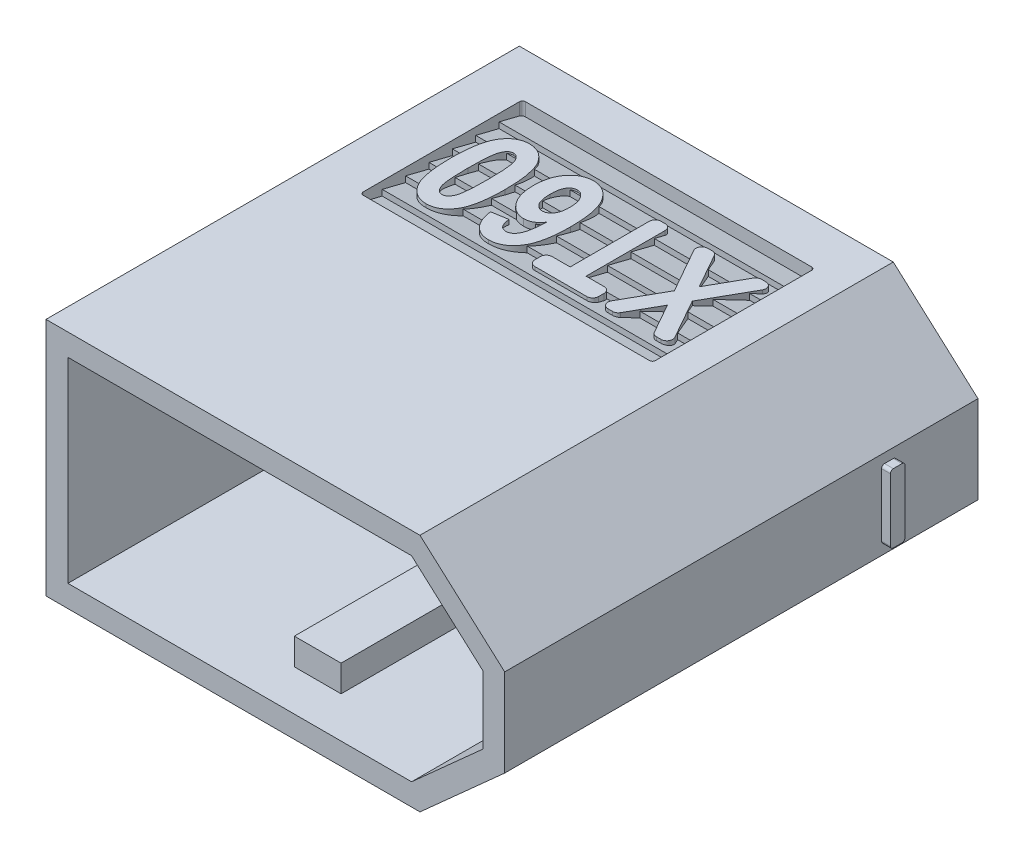
SolidWorks part; units mm, degrees
material "Nylon 101"
ref_plane "Plano frontal" through (0, 0, 0) normal (0, 0, 1) x (1, 0, 0)
ref_plane "Plano superior" through (0, 0, 0) normal (0, 1, 0) x (1, 0, 0)
ref_plane "Plano direito" through (0, 0, 0) normal (1, 0, 0) x (0, 0, -1)
sketch "Esboço1" plane through (0, 0, 0) normal (0, 0, 1) x (1, 0, 0)
  line L0 (0, 0) -> (12.8, 0)
  line L1 (12.8, 0) -> (15.7, 2.6)
  line L2 (15.7, 2.6) -> (15.7, 5.6)
  line L3 (15.7, 5.6) -> (12.8, 8.2)
  line L4 (12.8, 8.2) -> (0, 8.2)
  line L5 (0, 8.2) -> (0, 0)
  dimension "D1" = 12.8
  dimension "D2" = 3
  dimension "D3" = 15.7
  dimension "D4" = 8.2
extrude "Ressalto-extrusão1" add sketch "Esboço1" along normal blind 16.2
sketch "Esboço2" plane through (0, 0, 16.2) normal (0, 0, 1) x (1, 0, 0)
  line L0 (0.75, 7.45) -> (0.75, 0.75)
  line L1 (0.75, 0.75) -> (12.513, 0.75)
  line L2 (12.513, 0.75) -> (14.95, 2.9349)
  line L3 (14.95, 2.9349) -> (14.95, 5.2651)
  line L4 (14.95, 5.2651) -> (12.513, 7.45)
  line L5 (12.513, 7.45) -> (0.75, 7.45)
  line L6 (0, 8.2) -> (0, 0)
  line L7 (0, 0) -> (12.8, 0)
  line L8 (12.8, 0) -> (15.7, 2.6)
  line L9 (15.7, 2.6) -> (15.7, 5.6)
  line L10 (15.7, 5.6) -> (12.8, 8.2)
  line L11 (12.8, 8.2) -> (0, 8.2)
  line L12 (0, 8.2) -> (0, 0) construction
  line L13 (0, 0) -> (12.8, 0) construction
  line L14 (12.8, 0) -> (15.7, 2.6) construction
  line L15 (15.7, 2.6) -> (15.7, 5.6) construction
  line L16 (15.7, 5.6) -> (12.8, 8.2) construction
  line L17 (12.8, 8.2) -> (0, 8.2) construction
  dimension "D1" = 0
  dimension "D2" = 0.75
extrude "Corte-extrusão1" cut sketch "Esboço2" against normal blind 9.4
sketch "Esboço3" plane through (0, 0, 6.8) normal (0, 0, 1) x (1, 0, 0)
  line L1 (7.1, 1.66) -> (8.7, 1.66)
  line L2 (7.1, 1.66) -> (7.1, 0.75)
  line L3 (7.1, 0.75) -> (8.7, 0.75)
  line L4 (8.7, 1.66) -> (8.7, 0.75)
  line L7 (0.75, 0.75) -> (12.513, 0.75) construction
  line L8 (0, 0) -> (12.8, 0) construction
  line L9 (0, 8.2) -> (0, 0) construction
  dimension "D1" = 1.6
  dimension "D2" = 1.66
  dimension "D3" = 8.7
extrude "Ressalto-extrusão2" add sketch "Esboço3" along normal blind 8
sketch "Esboço4" plane through (0, 0, 6.8) normal (0, 0, 1) x (1, 0, 0)
  line L0 (12.513, 7.45) -> (0.75, 7.45) construction
  line L1 (8.7, 1.75) -> (7.1, 1.75)
  line L2 (8.7, 1.75) -> (8.7, 6.45)
  line L3 (8.7, 6.45) -> (7.1, 6.45)
  line L4 (7.1, 1.75) -> (7.1, 6.45)
  line L5 (0.75, 0.75) -> (7.1, 0.75) construction
  line L7 (7.1, 1.66) -> (7.1, 0.75) construction
  line L8 (8.7, 0.75) -> (8.7, 1.66) construction
  dimension "D1" = 1
  dimension "D2" = 1
extrude "Corte-extrusão2" cut sketch "Esboço4" against normal blind 1.5
sketch "Esboço5" plane through (0, 0, 0) normal (0, 0, -1) x (-1, 0, 0)
  line L0 (-15.7, 2.6) -> (-15.7, 5.6) construction
  line L3 (0, 8.2) -> (0, 0) construction
  circle A0 centre (-11.35, 4.1) radius 3
  circle A1 centre (-4.25, 4.1) radius 3
  point P6 (-15.7, 4.1)
  point P9 (-15.7, 4.1)
  dimension "D1" = 6
  dimension "D3" = 4.25
  dimension "D2" = 4.35
extrude "Corte-extrusão3" cut sketch "Esboço5" against normal blind 2
sketch "Esboço6" plane through (0, 0, 2) normal (0, 0, -1) x (-1, 0, 0)
  line L0 (-15.7, 2.6) -> (-15.7, 5.6) construction
  line L3 (0, 8.2) -> (0, 0) construction
  circle A0 centre (-11.35, 4.1) radius 2.15
  circle A2 centre (-4.25, 4.1) radius 2.15
  point P4 (-15.7, 4.1)
  dimension "D1" = 4.3
  dimension "D2" = 6.5
  dimension "D3" = 6.4
extrude "Corte-extrusão4" cut sketch "Esboço6" against normal through all
sketch "Esboço7" plane through (0, 0, 0) normal (-1, 0, 0) x (0, 0, 1)
  line L0 (2.8, 4.35) -> (2.05, 4.35)
  line L1 (4.25, 4.35) -> (3.5, 4.35)
  line L2 (4.35, 4.25) -> (4.35, 3.95)
  line L3 (4.25, 3.85) -> (3.5, 3.85)
  line L4 (1.95, 4.25) -> (1.95, 3.95)
  line L5 (3.3, 5.3) -> (3, 5.3)
  line L6 (3.4, 5.2) -> (3.4, 4.45)
  line L7 (3.3, 2.9) -> (3, 2.9)
  line L8 (2.9, 5.2) -> (2.9, 4.45)
  line L9 (2.8, 3.85) -> (2.05, 3.85)
  line L10 (3.4, 3.75) -> (3.4, 3)
  line L11 (2.9, 3.75) -> (2.9, 3)
  line L12 (0, 8.2) -> (0, 0) construction
  arc A0 (3, 2.9) -> (2.9, 3) centre (3, 3) cw
  arc A1 (3.3, 5.3) -> (3.4, 5.2) centre (3.3, 5.2) cw
  arc A2 (3, 5.3) -> (2.9, 5.2) centre (3, 5.2) ccw
  arc A3 (2.05, 4.35) -> (1.95, 4.25) centre (2.05, 4.25) ccw
  arc A4 (2.05, 3.85) -> (1.95, 3.95) centre (2.05, 3.95) cw
  arc A5 (2.8, 3.85) -> (2.9, 3.75) centre (2.8, 3.75) cw
  arc A6 (2.8, 4.35) -> (2.9, 4.45) centre (2.8, 4.45) ccw
  arc A7 (3.5, 3.85) -> (3.4, 3.75) centre (3.5, 3.75) ccw
  arc A8 (3.4, 3) -> (3.3, 2.9) centre (3.3, 3) cw
  arc A9 (4.35, 3.95) -> (4.25, 3.85) centre (4.25, 3.95) cw
  arc A10 (4.25, 4.35) -> (4.35, 4.25) centre (4.25, 4.25) cw
  arc A11 (3.5, 4.35) -> (3.4, 4.45) centre (3.5, 4.45) cw
  point P12 (1.95, 4.1)
  point P15 (0, 4.1)
  point P28 (2.9, 3.85)
  point P33 (3.4, 3.85)
  point P38 (4.35, 3.85)
  point P41 (4.35, 4.35)
  dimension "D4" = 0.1
  dimension "D1" = 2.4
  dimension "D2" = 0.5
  dimension "D3" = 4.35
extrude "Ressalto-extrusão3" add sketch "Esboço7" along normal blind 0.3
sketch "Esboço8" plane through (15.7, 0, 0) normal (1, 0, 0) x (0, 0, -1)
  line L0 (0, 2.6) -> (0, 5.6) construction
  line L1 (-3.2, 2.925) -> (-2.9, 2.925)
  line L2 (-3.3, 3.025) -> (-3.3, 5.175)
  line L3 (-3.2, 5.275) -> (-2.9, 5.275)
  line L4 (-2.8, 3.025) -> (-2.8, 5.175)
  arc A0 (-3.3, 5.175) -> (-3.2, 5.275) centre (-3.2, 5.175) cw
  arc A1 (-2.9, 5.275) -> (-2.8, 5.175) centre (-2.9, 5.175) cw
  arc A2 (-3.2, 2.925) -> (-3.3, 3.025) centre (-3.2, 3.025) cw
  arc A3 (-2.9, 2.925) -> (-2.8, 3.025) centre (-2.9, 3.025) ccw
  point P4 (-2.8, 4.1)
  point P7 (0, 4.1)
  point P10 (-3.3, 5.275)
  point P13 (-2.8, 5.275)
  point P18 (-2.8, 2.925)
  dimension "D4" = 0.1
  dimension "D1" = 2.35
  dimension "D2" = 0.5
  dimension "D3" = 3.3
extrude "Ressalto-extrusão4" add sketch "Esboço8" along normal blind 0.3
sketch "Esboço9" plane through (0, 0, 0) normal (0, -1, 0) x (1, 0, 0)
  line L0 (12.8, 16.2) -> (12.8, 0) construction
  line L1 (1.75, 7.0931) -> (11.55, 7.0931)
  line L2 (1.65, 6.9931) -> (1.65, 1.6431)
  line L3 (1.75, 1.5431) -> (11.55, 1.5431)
  line L4 (11.65, 6.9931) -> (11.65, 1.6431)
  arc A0 (1.65, 1.6431) -> (1.75, 1.5431) centre (1.75, 1.6431) ccw
  arc A1 (11.55, 1.5431) -> (11.65, 1.6431) centre (11.55, 1.6431) ccw
  arc A2 (11.55, 7.0931) -> (11.65, 6.9931) centre (11.55, 6.9931) cw
  arc A3 (1.75, 7.0931) -> (1.65, 6.9931) centre (1.75, 6.9931) ccw
  dimension "D1" = 0.1
  dimension "D2" = 1.15
  dimension "D3" = 10
  dimension "D4" = 5.55
extrude "Corte-extrusão5" cut sketch "Esboço9" against normal blind 0.75
sketch "Esboço10" plane through (1.65, 0, 0) normal (1, 0, 0) x (0, 0, -1)
  line L0 (-6.8, 0.75) -> (-1.6431, 0.75) construction
  line L1 (-1.5431, 0.75) -> (-1.5431, 0) construction
  line L2 (-3.1431, 0.25) -> (-2.3431, 0.45)
  line L3 (-2.3431, 0.45) -> (-2.3431, 0.25)
  line L5 (-3.1431, 0.45) -> (-3.1431, 0.25)
  line L6 (-2.3431, 0.45) -> (-2.3431, 0.25)
  line L7 (-3.9431, 0.25) -> (-3.1431, 0.45)
  line L8 (-3.9431, 0.45) -> (-3.9431, 0.25)
  line L9 (-4.7431, 0.25) -> (-3.9431, 0.45)
  line L10 (-4.7431, 0.45) -> (-4.7431, 0.25)
  line L11 (-5.5431, 0.25) -> (-4.7431, 0.45)
  line L12 (-5.5431, 0.45) -> (-5.5431, 0.25)
  line L13 (-6.3431, 0.25) -> (-5.5431, 0.45)
  line L14 (-6.3431, 0.45) -> (-6.3431, 0.25)
  line L15 (-7.1431, 0.25) -> (-6.3431, 0.45)
  line L16 (-7.1431, 0.45) -> (-7.1431, 0.25)
  line L17 (-7.1431, 0.45) -> (-7.1431, 0.75)
  line L19 (-2.3431, 0.25) -> (-1.5431, 0.45)
  line L20 (-7.1431, 0.75) -> (-1.5431, 0.75)
  line L21 (-1.5431, 0.45) -> (-1.5431, 0.75)
  line L31 (-2.3431, 0.25) -> (-1.5431, 0.45)
  line M62 (-1.6431, 0) -> (-1.6431, 0.75)
  line M63 (-1.6431, 0.75) -> (-6.8, 0.75)
  line M64 (-6.8, 0.75) -> (-6.9931, 0.75)
  line M65 (-6.9931, 0.75) -> (-6.9931, 0)
  dimension "D1" = 0.8
  dimension "D2" = 0.2
  dimension "D3" = 0.3
  dimension "D4" = 7
extrude "Ressalto-extrusão7" add sketch "Esboço10" along normal up to surface (10 mm away) contours L3 M65 M62 M63 M64 | M62 | M65 region at (1.65, 0.5464, 4.3262) region at (1.65, 0.5937, 1.5938) region at (1.65, 0.5093, 7.0691) up to face at (11.65, 0.45, 4.8145)
ref_plane "Plano1" through (0, 4.1, 0) normal (0, 1, 0) x (1, 0, 0)
mirror "Espelhar1" about plane through (0, 4.1, 0) normal (0, 1, 0) of "Corte-extrusão5", "Ressalto-extrusão7"
ref_plane "Plano2" through (0, 0.5, 0) normal (0, -1, 0) x (-1, 0, 0)
sketch "Esboço11" plane through (0, 0.5, 0) normal (0, -1, 0) x (-1, 0, 0)
  line L1 (-2.131, -7.0931) -> (-2.131, -1.5431) construction
  line L2 (-11.55, -7.0931) -> (-1.75, -7.0931) construction
  line L3 (-11.55, -1.5431) -> (-1.75, -1.5431) construction
  line L4 (-0.85, -6.1831) -> (-0.85, -2.4531) construction
  line L5 (-0.85, -2.4531) -> (-11.65, -2.4531) construction
  line L8 (-11.65, -3.1431) -> (-11.65, -2.3431) construction
  line L10 (-1.65, -6.9931) -> (-1.65, -1.6431) construction
  text T0 "<b><i>TGY</i></b>" font "Calibri" height in points 14
  point P8 (-0.85, -4.3181)
  point P9 (-2.131, -4.3181)
  dimension "D2" = 0.8
  dimension "D1" = 3.73
extrude "Ressalto-extrusão8" add sketch "Esboço11" along normal blind 0.3
ref_plane "Plano3" through (0, 7.7, 0) normal (0, 1, 0) x (1, 0, 0)
sketch "Esboço12" plane through (0, 7.7, 0) normal (0, 1, 0) x (1, 0, 0)
  line L0 (11.0942, -7.0931) -> (11.0942, -1.5431) construction
  line L1 (11.55, -7.0931) -> (1.75, -7.0931) construction
  line L3 (11.3535, -6.0681) -> (11.3535, -2.5681) construction
  line L6 (11.3535, -2.5681) -> (1.9746, -2.5681) construction
  line L7 (11.185, -2.8665) -> (10.3201, -4.3984)
  line L8 (10.3201, -4.3984) -> (11.0942, -5.7698)
  line L9 (10.92, -6.0681) -> (10.7649, -6.0681)
  line L10 (10.5908, -5.9665) -> (10.0126, -4.9431)
  line L11 (10.0126, -4.9431) -> (9.435, -5.9664)
  line L12 (9.2609, -6.0681) -> (9.1051, -6.0681)
  line L13 (8.931, -5.7698) -> (9.705, -4.3984)
  line L14 (9.705, -4.3984) -> (8.8401, -2.8665)
  line L15 (9.0143, -2.5681) -> (9.1699, -2.5681)
  line L16 (9.3441, -2.6698) -> (10.0126, -3.8543)
  line L17 (10.0126, -3.8543) -> (10.6817, -2.6698)
  line L18 (10.8559, -2.5681) -> (11.0109, -2.5681)
  line L19 (7.7626, -2.7681) -> (7.7626, -5.4772)
  line L20 (7.7626, -5.4772) -> (8.3808, -5.4772)
  line L21 (8.5808, -5.6772) -> (8.5808, -5.8681)
  line L22 (8.3808, -6.0681) -> (6.5989, -6.0681)
  line L23 (6.3989, -5.8681) -> (6.3989, -5.6772)
  line L24 (6.5989, -5.4772) -> (7.2171, -5.4772)
  line L25 (7.2171, -5.4772) -> (7.2171, -2.7681)
  line L26 (7.4171, -2.5681) -> (7.5626, -2.5681)
  line L27 (4.2171, -5.2045) -> (4.7626, -5.1136)
  line L28 (11.55, -1.5431) -> (1.75, -1.5431) construction
  arc A0 (7.2171, -2.7681) -> (7.4171, -2.5681) centre (7.4171, -2.7681) cw
  arc A1 (7.7626, -2.7681) -> (7.5626, -2.5681) centre (7.5626, -2.7681) ccw
  arc A2 (6.3989, -5.6772) -> (6.5989, -5.4772) centre (6.5989, -5.6772) cw
  arc A3 (6.5989, -6.0681) -> (6.3989, -5.8681) centre (6.5989, -5.8681) cw
  arc A4 (8.5808, -5.8681) -> (8.3808, -6.0681) centre (8.3808, -5.8681) cw
  arc A5 (8.3808, -5.4772) -> (8.5808, -5.6772) centre (8.3808, -5.6772) cw
  arc A6 (11.185, -2.8665) -> (11.0109, -2.5681) centre (11.0109, -2.7681) ccw
  arc A7 (10.6817, -2.6698) -> (10.8559, -2.5681) centre (10.8559, -2.7681) cw
  arc A8 (9.1699, -2.5681) -> (9.3441, -2.6698) centre (9.1699, -2.7681) cw
  arc A9 (8.8401, -2.8665) -> (9.0143, -2.5681) centre (9.0143, -2.7681) cw
  arc A10 (9.1051, -6.0681) -> (8.931, -5.7698) centre (9.1051, -5.8681) cw
  arc A11 (9.435, -5.9664) -> (9.2609, -6.0681) centre (9.2609, -5.8681) cw
  arc A12 (10.7649, -6.0681) -> (10.5908, -5.9665) centre (10.7649, -5.8681) cw
  arc A13 (11.0942, -5.7698) -> (10.92, -6.0681) centre (10.92, -5.8681) cw
  spline S0 degree 3 poles (4.7626, -5.1136) (4.7682, -5.1739) (4.7813, -5.2594) (4.8192, -5.3612) (4.8534, -5.4198) (4.8944, -5.4666) (4.9618, -5.511) (5.022, -5.5233) (5.0623, -5.5227) knots 0 0 0 0 0.323351 0.457032 0.575726 0.682828 0.785622 1 1 1 1
  spline S1 degree 3 poles (5.0623, -5.5227) (5.09, -5.5233) (5.1312, -5.5165) (5.1832, -5.4965) (5.2201, -5.4751) (5.2548, -5.4474) (5.2873, -5.4137) (5.3188, -5.3744) (5.3485, -5.328) (5.3759, -5.2719) (5.4005, -5.2044) (5.4208, -5.1242) (5.4414, -5.0325) (5.4567, -4.9277) (5.4769, -4.7639) (5.4853, -4.6343) (5.4898, -4.544) knots 0 0 0 0 0.071106 0.106432 0.143035 0.180361 0.220458 0.263402 0.309744 0.362096 0.423824 0.494518 0.575001 0.665718 0.767055 1 1 1 1
  spline S2 degree 3 poles (5.4898, -4.544) (5.4583, -4.5903) (5.407, -4.6546) (5.3276, -4.7255) (5.2671, -4.7681) (5.2028, -4.8002) (5.1126, -4.8326) (5.0401, -4.8399) (4.992, -4.8409) knots 0 0 0 0 0.277998 0.405178 0.526602 0.643637 0.760549 1 1 1 1
  spline S3 degree 3 poles (4.992, -4.8409) (4.9384, -4.84) (4.8576, -4.8324) (4.7559, -4.798) (4.6823, -4.7636) (4.6106, -4.7202) (4.5426, -4.6656) (4.4769, -4.602) (4.4148, -4.529) (4.3577, -4.4481) (4.3074, -4.36) (4.2661, -4.2652) (4.2305, -4.1646) (4.205, -4.0571) (4.1787, -3.9021) (4.1709, -3.7817) (4.1717, -3.6995) knots 0 0 0 0 0.103373 0.154207 0.205955 0.259297 0.315055 0.373347 0.435039 0.499095 0.563542 0.6298 0.697776 0.768574 0.842016 1 1 1 1
  spline S4 degree 3 poles (4.1717, -3.6995) (4.1719, -3.6124) (4.1791, -3.4851) (4.2059, -3.3214) (4.2344, -3.2096) (4.2696, -3.1044) (4.3147, -3.0075) (4.3663, -2.9169) (4.427, -2.8357) (4.4929, -2.7625) (4.5632, -2.698) (4.638, -2.6441) (4.7161, -2.5992) (4.7984, -2.5649) (4.9149, -2.5326) (5.0059, -2.5223) (5.0673, -2.5227) knots 0 0 0 0 0.157847 0.230497 0.300424 0.366636 0.431332 0.493809 0.555163 0.614703 0.672107 0.727719 0.78152 0.834986 0.88891 1 1 1 1
  spline S5 degree 3 poles (5.0673, -2.5227) (5.1348, -2.5224) (5.235, -2.5352) (5.3621, -2.5775) (5.4516, -2.6225) (5.5367, -2.6804) (5.6167, -2.7511) (5.6923, -2.8344) (5.764, -2.9301) (5.8292, -3.0408) (5.8839, -3.1688) (5.9316, -3.3125) (5.969, -3.4733) (5.9997, -3.6502) (6.0283, -3.9192) (6.0353, -4.1298) (6.0353, -4.2755) knots 0 0 0 0 0.090693 0.134685 0.17953 0.224913 0.272738 0.32276 0.375986 0.433204 0.49507 0.562819 0.636478 0.716918 0.804031 1 1 1 1
  spline S6 degree 3 poles (6.0353, -4.2755) (6.0353, -4.4236) (6.0286, -4.6379) (5.9972, -4.9112) (5.9666, -5.0917) (5.9263, -5.2555) (5.8779, -5.4031) (5.8201, -5.5343) (5.7518, -5.6479) (5.6774, -5.7469) (5.5976, -5.8325) (5.5132, -5.906) (5.4224, -5.9645) (5.3276, -6.0115) (5.1918, -6.0556) (5.0843, -6.0686) (5.0119, -6.0681) knots 0 0 0 0 0.192658 0.278521 0.357597 0.430563 0.497753 0.559502 0.616537 0.669747 0.720292 0.768555 0.814847 0.860431 0.905809 1 1 1 1
  spline S7 degree 3 poles (5.0119, -6.0681) (4.9619, -6.0679) (4.888, -6.0616) (4.793, -6.0396) (4.7258, -6.0161) (4.6619, -5.9851) (4.6002, -5.9489) (4.5418, -5.9054) (4.4872, -5.8546) (4.4355, -5.7981) (4.3903, -5.7331) (4.3488, -5.6621) (4.3131, -5.5835) (4.2805, -5.4988) (4.2454, -5.3724) (4.226, -5.2732) (4.2171, -5.2045) knots 0 0 0 0 0.115543 0.170649 0.225187 0.279791 0.334526 0.390474 0.447811 0.50673 0.567186 0.630471 0.696846 0.766493 0.839959 1 1 1 1
  spline S8 degree 3 poles (5.4444, -3.7215) (5.4434, -3.6718) (5.4418, -3.5989) (5.429, -3.5058) (5.4165, -3.4425) (5.399, -3.3843) (5.3797, -3.33) (5.3555, -3.2808) (5.3274, -3.2367) (5.298, -3.1971) (5.2668, -3.1628) (5.2343, -3.1343) (5.2019, -3.1095) (5.1674, -3.0908) (5.1199, -3.0739) (5.0828, -3.0683) (5.058, -3.0681) knots 0 0 0 0 0.178482 0.260709 0.336948 0.409468 0.478213 0.543503 0.605673 0.665087 0.720356 0.771459 0.82001 0.866345 0.91145 1 1 1 1
  spline S9 degree 3 poles (5.058, -3.0681) (5.0113, -3.0673) (4.9398, -3.0858) (4.8626, -3.147) (4.82, -3.1972) (4.7904, -3.2464) (4.7705, -3.2897) (4.7544, -3.3389) (4.7402, -3.3931) (4.7296, -3.4532) (4.7205, -3.5442) (4.7163, -3.6154) (4.7171, -3.6647) knots 0 0 0 0 0.182718 0.277312 0.381921 0.439334 0.501577 0.568146 0.641921 0.72105 0.806868 1 1 1 1
  spline S10 degree 3 poles (4.7171, -3.6647) (4.717, -3.7159) (4.7193, -3.7901) (4.7313, -3.8847) (4.7423, -3.9476) (4.7573, -4.005) (4.7747, -4.0573) (4.7959, -4.1039) (4.8285, -4.1562) (4.8734, -4.2114) (4.9574, -4.2751) (5.0328, -4.2967) (5.0829, -4.2954) knots 0 0 0 0 0.189208 0.273855 0.352112 0.425324 0.492836 0.555472 0.613995 0.720194 0.816437 1 1 1 1
  spline S11 degree 3 poles (5.0829, -4.2954) (5.1315, -4.2955) (5.2057, -4.2763) (5.2877, -4.2147) (5.333, -4.163) (5.3652, -4.1135) (5.3866, -4.0705) (5.4042, -4.0231) (5.4192, -3.9714) (5.4302, -3.915) (5.4422, -3.8316) (5.4445, -3.7663) (5.4444, -3.7215) knots 0 0 0 0 0.192976 0.293261 0.403879 0.464413 0.527516 0.593907 0.665362 0.741186 0.821937 1 1 1 1
  spline S12 degree 3 poles (2.8776, -6.0681) (2.8107, -6.0678) (2.7113, -6.0563) (2.586, -6.0147) (2.4983, -5.9711) (2.4159, -5.915) (2.3386, -5.8466) (2.2662, -5.766) (2.1985, -5.6725) (2.1376, -5.5631) (2.0855, -5.436) (2.0419, -5.2906) (2.0063, -5.1269) (1.978, -4.9448) (1.9513, -4.6654) (1.9446, -4.4461) (1.9444, -4.294) knots 0 0 0 0 0.08972 0.132871 0.17644 0.220536 0.26618 0.314488 0.365396 0.420661 0.481834 0.549191 0.623951 0.706175 0.796104 1 1 1 1
  spline S13 degree 3 poles (1.9444, -4.294) (1.9446, -4.1424) (1.9512, -3.9238) (1.9781, -3.6451) (2.0061, -3.4634) (2.0421, -3.2998) (2.0852, -3.1545) (2.1378, -3.0275) (2.1984, -2.9183) (2.2663, -2.8251) (2.3378, -2.744) (2.4152, -2.6758) (2.4975, -2.6199) (2.5847, -2.5759) (2.7095, -2.5348) (2.8083, -2.5226) (2.8748, -2.5227) knots 0 0 0 0 0.203744 0.29357 0.37599 0.450617 0.518438 0.579462 0.634858 0.685888 0.734097 0.77985 0.824051 0.867439 0.910692 1 1 1 1
  spline S14 degree 3 poles (2.8748, -2.5227) (2.9415, -2.5237) (3.0413, -2.5333) (3.1662, -2.5756) (3.2543, -2.618) (3.3363, -2.6745) (3.4139, -2.742) (3.4862, -2.8219) (3.5413, -2.8978) (3.5827, -2.965) (3.6116, -3.0212) (3.6385, -3.082) (3.6644, -3.1471) (3.6866, -3.2179) (3.708, -3.2929) (3.7271, -3.3725) (3.744, -3.4569) (3.76, -3.5458) (3.7721, -3.64) (3.784, -3.7384) (3.792, -3.842) (3.7994, -3.9499) (3.8057, -4.1036) (3.809, -4.221) (3.808, -4.3011) knots 0 0 0 0 0.089418 0.132451 0.175762 0.219738 0.26505 0.312991 0.363505 0.390209 0.418376 0.447842 0.479108 0.512034 0.546898 0.583358 0.621467 0.661946 0.704107 0.748387 0.794432 0.842956 0.893008 1 1 1 1
  spline S15 degree 3 poles (3.808, -4.3011) (3.8078, -4.4522) (3.8011, -4.6701) (3.7744, -4.9476) (3.7461, -5.1285) (3.7104, -5.2915) (3.6671, -5.4365) (3.6147, -5.5633) (3.554, -5.6725) (3.4861, -5.7657) (3.4146, -5.8468) (3.3372, -5.915) (3.255, -5.9709) (3.1677, -6.0149) (3.0429, -6.056) (2.9441, -6.0682) (2.8776, -6.0681) knots 0 0 0 0 0.203492 0.293171 0.375116 0.449884 0.517528 0.578668 0.634169 0.685295 0.733595 0.779434 0.823719 0.867188 0.910523 1 1 1 1
  spline S16 degree 3 poles (2.8762, -5.5227) (2.9014, -5.5225) (2.9391, -5.5157) (2.9853, -5.4936) (3.0177, -5.4696) (3.0472, -5.4386) (3.0753, -5.4017) (3.1015, -5.3582) (3.1264, -5.3061) (3.1493, -5.2412) (3.1662, -5.1592) (3.1829, -5.0598) (3.1947, -4.9418) (3.2056, -4.806) (3.2148, -4.5879) (3.2172, -4.4152) (3.2171, -4.294) knots 0 0 0 0 0.054972 0.082543 0.111449 0.142586 0.175843 0.2128 0.253578 0.301908 0.362982 0.436475 0.522453 0.622213 0.734739 1 1 1 1
  spline S17 degree 3 poles (3.2171, -4.294) (3.2172, -4.173) (3.2148, -4.0006) (3.2056, -3.7827) (3.1946, -3.6468) (3.1829, -3.5291) (3.1662, -3.4301) (3.1492, -3.3487) (3.1266, -3.2841) (3.1014, -3.2324) (3.0751, -3.189) (3.0477, -3.1515) (3.0174, -3.1212) (2.9854, -3.0972) (2.9391, -3.0752) (2.9014, -3.0683) (2.8762, -3.0681) knots 0 0 0 0 0.265262 0.378009 0.477964 0.564111 0.637236 0.697923 0.746348 0.786738 0.823768 0.857504 0.888332 0.917295 0.944921 1 1 1 1
  spline S18 degree 3 poles (2.8762, -3.0681) (2.8509, -3.0683) (2.8128, -3.0749) (2.7663, -3.0974) (2.7333, -3.1209) (2.7037, -3.1525) (2.675, -3.1892) (2.6497, -3.2336) (2.6244, -3.2852) (2.6028, -3.3503) (2.5854, -3.4315) (2.5689, -3.5305) (2.5569, -3.648) (2.5471, -3.7837) (2.5374, -4.001) (2.5353, -4.1732) (2.5353, -4.294) knots 0 0 0 0 0.055564 0.083174 0.11254 0.143719 0.17775 0.214492 0.255326 0.303553 0.364206 0.437289 0.523386 0.622727 0.735409 1 1 1 1
  spline S19 degree 3 poles (2.5353, -4.294) (2.5354, -4.4152) (2.5374, -4.5879) (2.5471, -4.8059) (2.5568, -4.9419) (2.5689, -5.0598) (2.5854, -5.1593) (2.6027, -5.241) (2.6243, -5.3063) (2.6498, -5.3579) (2.6747, -5.4022) (2.7039, -5.4384) (2.7333, -5.4699) (2.7663, -5.4934) (2.8128, -5.5158) (2.8509, -5.5225) (2.8762, -5.5227) knots 0 0 0 0 0.265055 0.377494 0.477137 0.563048 0.636484 0.697511 0.745634 0.78638 0.823042 0.856591 0.887703 0.917006 0.944556 1 1 1 1
  point P7 (11.0942, -4.3181)
  point P10 (11.3535, -4.3181)
  dimension "D2" = 0.2
  dimension "D1" = 3.5
extrude "Ressalto-extrusão9" add sketch "Esboço12" along normal blind 0.3
ref_plane "Plane1" through (0, 2.6, 0) normal (0, 1, 0) x (1, 0, 0)
